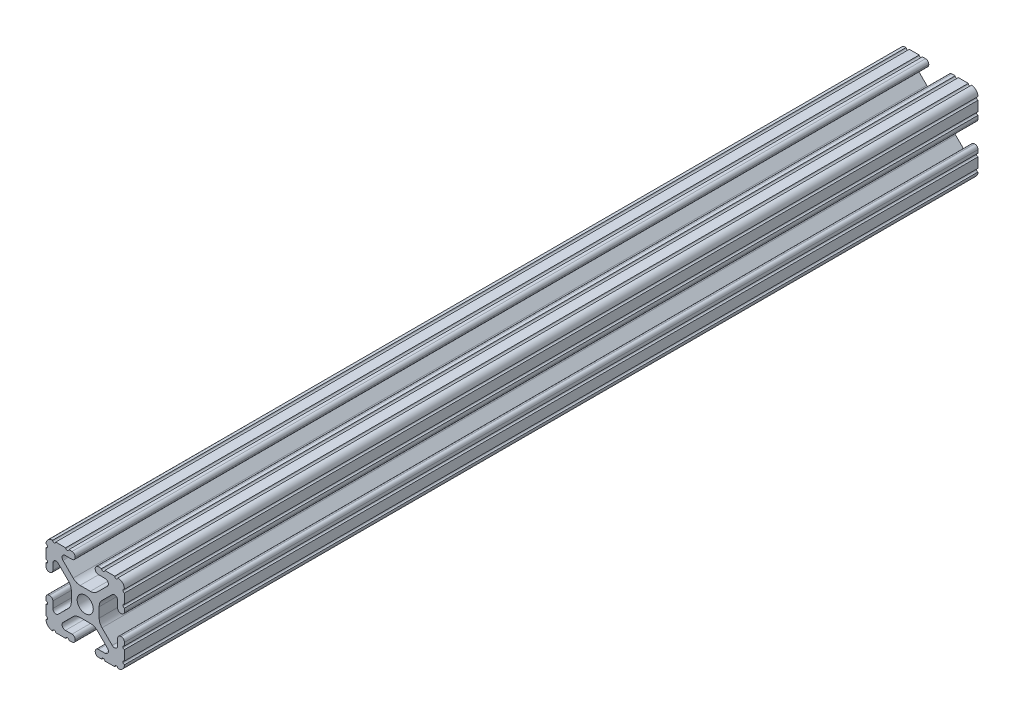
SolidWorks part; units mm, degrees
ref_plane "Front" through (0, 0, 0) normal (0, 0, 1) x (1, 0, 0)
ref_plane "Top" through (0, 0, 0) normal (0, 1, 0) x (1, 0, 0)
ref_plane "Right" through (0, 0, 0) normal (1, 0, 0) x (0, 0, -1)
sketch "Sketch1" plane through (0, 0, 0) normal (0, 0, 1) x (1, 0, 0)
  line L0 (-7.5107, 9.4563) -> (7.5107, 9.4563) construction
  line L1 (-7.4968, -9.4098) -> (7.4968, -9.4098) construction
  line L88 (-7.1797, -8.6452) -> (-3.9523, -5.4237)
  line L89 (-1.7093, -4.4958) -> (1.7093, -4.4958)
  line L90 (3.9523, -5.4237) -> (7.1797, -8.6452)
  line L91 (6.4164, -10.4902) -> (4.2875, -10.4902)
  line L92 (3.2385, -11.5392) -> (3.2385, -11.651)
  line L93 (4.2875, -12.7) -> (5.3171, -12.7)
  line L94 (6.3331, -12.7) -> (9.5504, -12.7)
  line L95 (12.7, -9.5504) -> (12.7, -6.3331)
  line L96 (12.7, -5.3171) -> (12.7, -4.2875)
  line L97 (11.651, -3.2385) -> (11.5392, -3.2385)
  line L98 (10.4902, -4.2875) -> (10.4902, -6.4021)
  line L99 (8.7371, -7.1294) -> (5.441, -3.8408)
  line L100 (4.5085, -1.5932) -> (4.5085, 1.5932)
  line L101 (5.441, 3.8408) -> (8.7371, 7.1294)
  line L102 (10.4902, 6.4021) -> (10.4902, 4.2875)
  line L103 (11.5392, 3.2385) -> (11.651, 3.2385)
  line L104 (12.7, 4.2875) -> (12.7, 5.3171)
  line L105 (12.7, 6.3331) -> (12.7, 9.5504)
  line L106 (9.5504, 12.7) -> (6.3331, 12.7)
  line L107 (5.3171, 12.7) -> (4.2875, 12.7)
  line L108 (3.2385, 11.651) -> (3.2385, 11.5392)
  line L109 (4.2875, 10.4902) -> (6.4768, 10.4902)
  line L110 (7.207, 8.7244) -> (3.8983, 5.4232)
  line L111 (1.6558, 4.4958) -> (-1.6558, 4.4958)
  line L112 (-3.8983, 5.4232) -> (-7.207, 8.7244)
  line L113 (-6.4768, 10.4902) -> (-4.2875, 10.4902)
  line L114 (-3.2385, 11.5392) -> (-3.2385, 11.651)
  line L115 (-4.2875, 12.7) -> (-5.3171, 12.7)
  line L116 (-6.3331, 12.7) -> (-9.5504, 12.7)
  line L117 (-12.7, 9.5504) -> (-12.7, 6.3331)
  line L118 (-12.7, 5.3171) -> (-12.7, 4.2875)
  line L119 (-11.651, 3.2385) -> (-11.5392, 3.2385)
  line L120 (-10.4902, 4.2875) -> (-10.4902, 6.4021)
  line L121 (-8.7371, 7.1294) -> (-5.441, 3.8408)
  line L122 (-4.5085, 1.5932) -> (-4.5085, -1.5932)
  line L123 (-5.441, -3.8408) -> (-8.7371, -7.1294)
  line L124 (-10.4902, -6.4021) -> (-10.4902, -4.2875)
  line L125 (-11.5392, -3.2385) -> (-11.651, -3.2385)
  line L126 (-12.7, -4.2875) -> (-12.7, -5.3171)
  line L127 (-12.7, -6.3331) -> (-12.7, -9.5504)
  line L128 (-9.5504, -12.7) -> (-6.3331, -12.7)
  line L129 (-5.3171, -12.7) -> (-4.2875, -12.7)
  line L130 (-3.2385, -11.651) -> (-3.2385, -11.5392)
  line L131 (-4.2875, -10.4902) -> (-6.4164, -10.4902)
  circle A1 centre (0, 0) radius 2.6035
  arc A104 (-7.1797, -8.6452) -> (-6.4164, -10.4902) centre (-6.4164, -9.4098) ccw
  arc A105 (-1.7093, -4.4958) -> (-3.9523, -5.4237) centre (-1.7093, -7.6708) ccw
  arc A106 (3.9523, -5.4237) -> (1.7093, -4.4958) centre (1.7093, -7.6708) ccw
  arc A107 (6.4164, -10.4902) -> (7.1797, -8.6452) centre (6.4164, -9.4098) ccw
  arc A108 (4.2875, -10.4902) -> (3.2385, -11.5392) centre (4.2875, -11.5392) ccw
  arc A109 (3.2385, -11.651) -> (4.2875, -12.7) centre (4.2875, -11.651) ccw
  arc A110 (6.3331, -12.7) -> (5.3171, -12.7) centre (5.8251, -12.7) ccw
  arc A111 (10.5664, -12.6998) -> (9.5504, -12.7) centre (10.0584, -12.7) ccw
  arc A112 (10.5664, -12.6998) -> (12.6998, -10.5664) centre (10.5918, -10.5918) ccw
  arc A113 (12.7, -9.5504) -> (12.6998, -10.5664) centre (12.7, -10.0584) ccw
  arc A114 (12.7, -5.3171) -> (12.7, -6.3331) centre (12.7, -5.8251) ccw
  arc A115 (12.7, -4.2875) -> (11.651, -3.2385) centre (11.651, -4.2875) ccw
  arc A116 (11.5392, -3.2385) -> (10.4902, -4.2875) centre (11.5392, -4.2875) ccw
  arc A117 (8.7371, -7.1294) -> (10.4902, -6.4021) centre (9.4628, -6.4021) ccw
  arc A118 (4.5085, -1.5932) -> (5.441, -3.8408) centre (7.6835, -1.5932) ccw
  arc A119 (5.441, 3.8408) -> (4.5085, 1.5932) centre (7.6835, 1.5932) ccw
  arc A120 (10.4902, 6.4021) -> (8.7371, 7.1294) centre (9.4628, 6.4021) ccw
  arc A121 (10.4902, 4.2875) -> (11.5392, 3.2385) centre (11.5392, 4.2875) ccw
  arc A122 (11.651, 3.2385) -> (12.7, 4.2875) centre (11.651, 4.2875) ccw
  arc A123 (12.7, 6.3331) -> (12.7, 5.3171) centre (12.7, 5.8251) ccw
  arc A124 (12.6998, 10.5664) -> (12.7, 9.5504) centre (12.7, 10.0584) ccw
  arc A125 (12.6998, 10.5664) -> (10.5664, 12.6998) centre (10.5918, 10.5918) ccw
  arc A126 (9.5504, 12.7) -> (10.5664, 12.6998) centre (10.0584, 12.7) ccw
  arc A127 (5.3171, 12.7) -> (6.3331, 12.7) centre (5.8251, 12.7) ccw
  arc A128 (4.2875, 12.7) -> (3.2385, 11.651) centre (4.2875, 11.651) ccw
  arc A129 (3.2385, 11.5392) -> (4.2875, 10.4902) centre (4.2875, 11.5392) ccw
  arc A130 (7.207, 8.7244) -> (6.4768, 10.4902) centre (6.4768, 9.4563) ccw
  arc A131 (1.6558, 4.4958) -> (3.8983, 5.4232) centre (1.6558, 7.6708) ccw
  arc A132 (-3.8983, 5.4232) -> (-1.6558, 4.4958) centre (-1.6558, 7.6708) ccw
  arc A133 (-6.4768, 10.4902) -> (-7.207, 8.7244) centre (-6.4768, 9.4563) ccw
  arc A134 (-4.2875, 10.4902) -> (-3.2385, 11.5392) centre (-4.2875, 11.5392) ccw
  arc A135 (-3.2385, 11.651) -> (-4.2875, 12.7) centre (-4.2875, 11.651) ccw
  arc A136 (-6.3331, 12.7) -> (-5.3171, 12.7) centre (-5.8251, 12.7) ccw
  arc A137 (-10.5664, 12.6998) -> (-9.5504, 12.7) centre (-10.0584, 12.7) ccw
  arc A138 (-10.5664, 12.6998) -> (-12.6998, 10.5664) centre (-10.5918, 10.5918) ccw
  arc A139 (-12.7, 9.5504) -> (-12.6998, 10.5664) centre (-12.7, 10.0584) ccw
  arc A140 (-12.7, 5.3171) -> (-12.7, 6.3331) centre (-12.7, 5.8251) ccw
  arc A141 (-12.7, 4.2875) -> (-11.651, 3.2385) centre (-11.651, 4.2875) ccw
  arc A142 (-11.5392, 3.2385) -> (-10.4902, 4.2875) centre (-11.5392, 4.2875) ccw
  arc A143 (-8.7371, 7.1294) -> (-10.4902, 6.4021) centre (-9.4628, 6.4021) ccw
  arc A144 (-4.5085, 1.5932) -> (-5.441, 3.8408) centre (-7.6835, 1.5932) ccw
  arc A145 (-5.441, -3.8408) -> (-4.5085, -1.5932) centre (-7.6835, -1.5932) ccw
  arc A146 (-10.4902, -6.4021) -> (-8.7371, -7.1294) centre (-9.4628, -6.4021) ccw
  arc A147 (-10.4902, -4.2875) -> (-11.5392, -3.2385) centre (-11.5392, -4.2875) ccw
  arc A148 (-11.651, -3.2385) -> (-12.7, -4.2875) centre (-11.651, -4.2875) ccw
  arc A149 (-12.7, -6.3331) -> (-12.7, -5.3171) centre (-12.7, -5.8251) ccw
  arc A150 (-12.6998, -10.5664) -> (-12.7, -9.5504) centre (-12.7, -10.0584) ccw
  arc A151 (-12.6998, -10.5664) -> (-10.5664, -12.6998) centre (-10.5918, -10.5918) ccw
  arc A152 (-9.5504, -12.7) -> (-10.5664, -12.6998) centre (-10.0584, -12.7) ccw
  arc A153 (-5.3171, -12.7) -> (-6.3331, -12.7) centre (-5.8251, -12.7) ccw
  arc A154 (-4.2875, -12.7) -> (-3.2385, -11.651) centre (-4.2875, -11.651) ccw
  arc A155 (-3.2385, -11.5392) -> (-4.2875, -10.4902) centre (-4.2875, -11.5392) ccw
extrude "Boss-Extrude1" add sketch "Sketch1" along normal mid plane 914.4
sketch "Sketch3" plane through (-12.7, 0, 0) normal (-1, 0, 0) x (0, 0, 1)
  line L0 (-203.2, -25.4) -> (-203.2, 21.1581) construction
  line L1 (-203.2, -27.5528) -> (-203.2, 21.1581)
  line L2 (-203.2, 21.1581) -> (-461.0909, 21.1581)
  line L3 (-461.0909, 21.1581) -> (-461.0909, -25.4)
  line L4 (-461.0909, -25.4) -> (-203.2, -27.5528)
extrude "Cut-Extrude2" cut sketch "Sketch3" against normal blind 26.924 and the other way blind 4.318
sketch "Sketch5" plane through (12.7, 0, 0) normal (1, 0, 0) x (0, 0, -1)
  line L0 (-180.8558, -19.3511) -> (-180.8558, 304.1981) construction
  line L1 (-180.8558, -19.3511) -> (208.319, -19.3511)
  line L2 (208.319, -19.3511) -> (208.319, 23.9761)
  line L3 (208.319, 23.9761) -> (-180.8558, 23.9761)
  line L4 (-180.8558, 23.9761) -> (-180.8558, -19.3511)
  point P5 (0, 0)
  point P6 (-180.8558, 304.1981)
extrude "Cut-Extrude3" cut sketch "Sketch5" against normal through all
